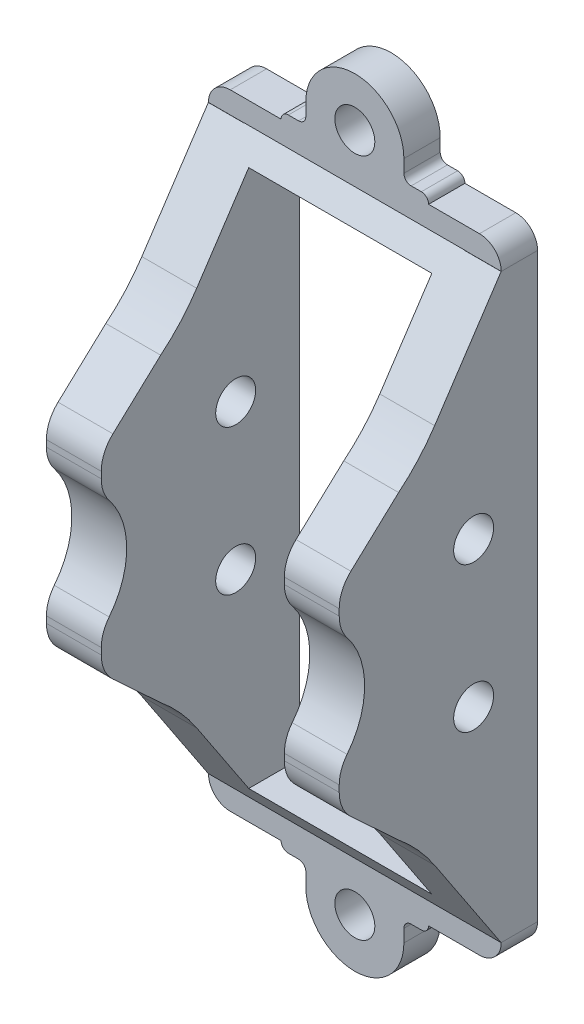
SolidWorks part; units mm, degrees
ref_plane "Front Plane" through (0, 0, 0) normal (0, 0, 1) x (1, 0, 0)
ref_plane "Top Plane" through (0, 0, 0) normal (0, 1, 0) x (1, 0, 0)
ref_plane "Right Plane" through (0, 0, 0) normal (1, 0, 0) x (0, 0, -1)
sketch "Sketch2" plane through (0, 0, 0) normal (0, 0, 1) x (1, 0, 0)
  line L0 (-58.75, 18.25) -> (-58.75, 111.75)
  line L1 (-45.25, 111.75) -> (-45.25, 18.25)
  line L3 (-56.225, 25) -> (-47.775, 25)
  line L4 (-56.225, 25) -> (-56.225, 105)
  line L5 (-56.225, 105) -> (-47.775, 105)
  line L6 (-47.775, 25) -> (-47.775, 105)
  circle A0 centre (-52, 18.25) radius 2.75
  circle A1 centre (-52, 111.75) radius 2.75
  arc A2 (-45.25, 111.75) -> (-58.75, 111.75) centre (-52, 111.75) ccw
  arc A3 (-58.75, 18.25) -> (-45.25, 18.25) centre (-52, 18.25) ccw
  circle A4 centre (-52, 18.25) radius 6.75 construction
  circle A5 centre (-52, 111.75) radius 6.75 construction
  dimension "D1" = 4
extrude "Boss-Extrude1" add sketch "Sketch2" along normal blind 5
sketch "Sketch4" plane through (0, 0, 0) normal (0, 0, 1) x (1, 0, 0)
  line L1 (-52, 21) -> (-62.15, 21)
  line L2 (-62.15, 118.5) -> (-62.15, 75) construction
  line L3 (-62.15, 21) -> (-41.85, 21)
  line L4 (-41.85, 118.5) -> (-41.85, 75) construction
  line L5 (-52, 109) -> (-62.15, 109)
  line L6 (-62.15, 109) -> (-41.85, 109)
  line L7 (-41.85, 109) -> (-41.85, 21)
  line L8 (-62.15, 21) -> (-62.15, 109)
  circle A0 centre (-52, 18.25) radius 2.75 construction
  circle A1 centre (-52, 111.75) radius 2.75 construction
extrude "Boss-Extrude2" add sketch "Sketch4" along normal up to surface (5 mm away) up to face at (-49.25, 18.25, 5)
sketch "Sketch5" plane through (-41.85, 0, 0) normal (1, 0, 0) x (0, 0, -1)
  line L1 (-5, 21) -> (-5, 109) construction
  line L2 (-5, 24.978) -> (-5, 105.022)
  line L5 (-30, 75.022) -> (-30, 80.5271)
  line L10 (-30, 54.978) -> (-30, 49.4729)
  line L11 (-30, 75.022) -> (-30, 80.5271)
  line L12 (-14.1667, 38.7973) -> (-5, 24.978)
  line L15 (-14.1667, 91.2027) -> (-5, 105.022)
  arc A0 (-30, 54.978) -> (-30, 75.022) centre (-35, 65) ccw
  arc A1 (-30, 80.5271) -> (-14.1667, 91.2027) centre (-35, 105.022) ccw
  arc A2 (-14.1667, 38.7973) -> (-30, 49.4729) centre (-35, 24.978) ccw
  line M14 (-5, 109) -> (-5, 21)
  dimension "D2" = 22.4
  dimension "D6" = 50
extrude "Boss-Extrude3" add sketch "Sketch5" against normal up to surface (20.3 mm away) contours A2 L12 L15 A1 L5 A0 L10 M14 up to face at (-62.15, 65, 2.5)
fillet "Fillet3" radius 4.2 4 edges at (-52, 80.5271, 30) (-52, 54.978, 30) (-52, 75.022, 30) (-52, 49.4729, 30)
sketch "Sketch7" plane through (0, 0, 5) normal (0, 0, -1) x (-1, 0, 0)
  line L1 (47.775, 25) -> (56.225, 25)
  line L2 (47.775, 25) -> (47.775, 105)
  line L3 (47.775, 105) -> (56.225, 105)
  line L4 (56.225, 25) -> (56.225, 105)
extrude "Cut-Extrude1" cut sketch "Sketch7" against normal blind 38
fillet "Fillet4" radius 3 4 edges at (-47.775, 105, 2.5073) (-56.225, 105, 2.5073) (-56.225, 25, 2.5073) (-47.775, 25, 2.5073)
fillet "Fillet5" radius 1 8 edges at (-62.15, 109, 2.5) (-58.75, 109, 2.5) (-45.25, 109, 2.5) (-41.85, 109, 2.5) (-62.15, 21, 2.5) (-58.75, 21, 2.5) (-41.85, 21, 2.5) (-45.25, 21, 2.5)
sketch "Sketch8" plane through (-41.85, 0, 0) normal (1, 0, 0) x (0, 0, -1)
  line L7 (0, 22) -> (0, 108)
  line L8 (0, 108) -> (-5, 108)
  line L9 (-5, 108) -> (-5, 105.022)
  line L10 (-5, 105.022) -> (-14.1667, 91.2027)
  line L11 (-14.1667, 38.7973) -> (-5, 24.978)
  line L12 (-5, 24.978) -> (-5, 22)
  line L13 (-5, 22) -> (0, 22)
  line L14 (0, 22) -> (0, 108)
  line L15 (0, 108) -> (-5, 108)
  line L16 (-5, 108) -> (-5, 105.022)
  line L17 (-5, 105.022) -> (-14.1667, 91.2027)
  line L18 (-14.1667, 38.7973) -> (-5, 24.978)
  line L19 (-5, 24.978) -> (-5, 22)
  line L20 (-5, 22) -> (0, 22)
  arc A7 (-27.1233, 81.2953) -> (-14.1667, 91.2027) centre (-35, 105.022) ccw
  arc A8 (-27.1233, 81.2953) -> (-30, 77.3295) centre (-25.8, 77.3092) ccw
  arc A9 (-30, 77.3295) -> (-28.3091, 73.9817) centre (-25.8, 77.3499) ccw
  arc A10 (-28.3091, 56.0183) -> (-28.3091, 73.9817) centre (-35, 65) ccw
  arc A11 (-28.3091, 56.0183) -> (-30, 52.6705) centre (-25.8, 52.6501) ccw
  arc A12 (-30, 52.6705) -> (-27.1233, 48.7047) centre (-25.8, 52.6908) ccw
  arc A13 (-14.1667, 38.7973) -> (-27.1233, 48.7047) centre (-35, 24.978) ccw
  arc A14 (-27.1233, 81.2953) -> (-14.1667, 91.2027) centre (-35, 105.022) ccw
  arc A15 (-27.1233, 81.2953) -> (-30, 77.3295) centre (-25.8, 77.3092) ccw
  arc A16 (-30, 77.3295) -> (-28.3091, 73.9817) centre (-25.8, 77.3499) ccw
  arc A17 (-28.3091, 56.0183) -> (-28.3091, 73.9817) centre (-35, 65) ccw
  arc A18 (-28.3091, 56.0183) -> (-30, 52.6705) centre (-25.8, 52.6501) ccw
  arc A19 (-30, 52.6705) -> (-27.1233, 48.7047) centre (-25.8, 52.6908) ccw
  arc A20 (-14.1667, 38.7973) -> (-27.1233, 48.7047) centre (-35, 24.978) ccw
  dimension "D1" = 0
extrude "Boss-Extrude4" add sketch "Sketch8" along normal blind 5
sketch "Sketch9" plane through (-62.15, 0, 0) normal (-1, 0, 0) x (0, 0, 1)
  line L7 (5, 105.022) -> (5, 108)
  line L8 (5, 108) -> (0, 108)
  line L9 (0, 108) -> (0, 22)
  line L10 (0, 22) -> (5, 22)
  line L11 (5, 22) -> (5, 24.978)
  line L12 (5, 24.978) -> (14.1667, 38.7973)
  line L13 (14.1667, 91.2027) -> (5, 105.022)
  line L14 (5, 105.022) -> (5, 108)
  line L15 (5, 108) -> (0, 108)
  line L16 (0, 108) -> (0, 22)
  line L17 (0, 22) -> (5, 22)
  line L18 (5, 22) -> (5, 24.978)
  line L19 (5, 24.978) -> (14.1667, 38.7973)
  line L20 (14.1667, 91.2027) -> (5, 105.022)
  arc A7 (27.1233, 48.7047) -> (14.1667, 38.7973) centre (35, 24.978) ccw
  arc A8 (27.1233, 48.7047) -> (30, 52.6705) centre (25.8, 52.6908) ccw
  arc A9 (30, 52.6705) -> (28.3091, 56.0183) centre (25.8, 52.6501) ccw
  arc A10 (28.3091, 73.9817) -> (28.3091, 56.0183) centre (35, 65) ccw
  arc A11 (28.3091, 73.9817) -> (30, 77.3295) centre (25.8, 77.3499) ccw
  arc A12 (30, 77.3295) -> (27.1233, 81.2953) centre (25.8, 77.3092) ccw
  arc A13 (14.1667, 91.2027) -> (27.1233, 81.2953) centre (35, 105.022) ccw
  arc A14 (27.1233, 48.7047) -> (14.1667, 38.7973) centre (35, 24.978) ccw
  arc A15 (27.1233, 48.7047) -> (30, 52.6705) centre (25.8, 52.6908) ccw
  arc A16 (30, 52.6705) -> (28.3091, 56.0183) centre (25.8, 52.6501) ccw
  arc A17 (28.3091, 73.9817) -> (28.3091, 56.0183) centre (35, 65) ccw
  arc A18 (28.3091, 73.9817) -> (30, 77.3295) centre (25.8, 77.3499) ccw
  arc A19 (30, 77.3295) -> (27.1233, 81.2953) centre (25.8, 77.3092) ccw
  arc A20 (14.1667, 91.2027) -> (27.1233, 81.2953) centre (35, 105.022) ccw
  dimension "D1" = 0
extrude "Boss-Extrude5" add sketch "Sketch9" along normal blind 5
sketch "Sketch10" plane through (-47.775, 0, 0) normal (-1, 0, 0) x (0, 0, 1)
  line L5 (14.1667, 91.2027) -> (7.0046, 102)
  line L6 (7.0046, 102) -> (0, 102)
  line L7 (0, 102) -> (0, 28)
  line L8 (0, 28) -> (7.0046, 28)
  line L9 (7.0046, 28) -> (14.1667, 38.7973)
  line L10 (14.1667, 91.2027) -> (7.0046, 102)
  line L11 (7.0046, 102) -> (0, 102)
  line L12 (0, 102) -> (0, 28)
  line L13 (0, 28) -> (7.0046, 28)
  line L14 (7.0046, 28) -> (14.1667, 38.7973)
  arc A7 (27.1233, 48.7047) -> (14.1667, 38.7973) centre (35, 24.978) ccw
  arc A8 (27.1233, 48.7047) -> (30, 52.6705) centre (25.8, 52.6908) ccw
  arc A9 (30, 52.6705) -> (28.3091, 56.0183) centre (25.8, 52.6501) ccw
  arc A10 (28.3091, 73.9817) -> (28.3091, 56.0183) centre (35, 65) ccw
  arc A11 (28.3091, 73.9817) -> (30, 77.3295) centre (25.8, 77.3499) ccw
  arc A12 (30, 77.3295) -> (27.1233, 81.2953) centre (25.8, 77.3092) ccw
  arc A13 (14.1667, 91.2027) -> (27.1233, 81.2953) centre (35, 105.022) ccw
  arc A14 (27.1233, 48.7047) -> (14.1667, 38.7973) centre (35, 24.978) ccw
  arc A15 (27.1233, 48.7047) -> (30, 52.6705) centre (25.8, 52.6908) ccw
  arc A16 (30, 52.6705) -> (28.3091, 56.0183) centre (25.8, 52.6501) ccw
  arc A17 (28.3091, 73.9817) -> (28.3091, 56.0183) centre (35, 65) ccw
  arc A18 (28.3091, 73.9817) -> (30, 77.3295) centre (25.8, 77.3499) ccw
  arc A19 (30, 77.3295) -> (27.1233, 81.2953) centre (25.8, 77.3092) ccw
  arc A20 (14.1667, 91.2027) -> (27.1233, 81.2953) centre (35, 105.022) ccw
  dimension "D1" = 0
extrude "Cut-Extrude2" cut sketch "Sketch10" against normal blind 5
sketch "Sketch11" plane through (-56.225, 0, 0) normal (1, 0, 0) x (0, 0, -1)
  line L5 (0, 28) -> (0, 102)
  line L6 (0, 102) -> (-7.0046, 102)
  line L7 (-7.0046, 102) -> (-14.1667, 91.2027)
  line L8 (-14.1667, 38.7973) -> (-7.0046, 28)
  line L9 (-7.0046, 28) -> (0, 28)
  line L10 (0, 28) -> (0, 102)
  line L11 (0, 102) -> (-7.0046, 102)
  line L12 (-7.0046, 102) -> (-14.1667, 91.2027)
  line L13 (-14.1667, 38.7973) -> (-7.0046, 28)
  line L14 (-7.0046, 28) -> (0, 28)
  arc A7 (-27.1233, 81.2953) -> (-14.1667, 91.2027) centre (-35, 105.022) ccw
  arc A8 (-27.1233, 81.2953) -> (-30, 77.3295) centre (-25.8, 77.3092) ccw
  arc A9 (-30, 77.3295) -> (-28.3091, 73.9817) centre (-25.8, 77.3499) ccw
  arc A10 (-28.3091, 56.0183) -> (-28.3091, 73.9817) centre (-35, 65) ccw
  arc A11 (-28.3091, 56.0183) -> (-30, 52.6705) centre (-25.8, 52.6501) ccw
  arc A12 (-30, 52.6705) -> (-27.1233, 48.7047) centre (-25.8, 52.6908) ccw
  arc A13 (-14.1667, 38.7973) -> (-27.1233, 48.7047) centre (-35, 24.978) ccw
  arc A14 (-27.1233, 81.2953) -> (-14.1667, 91.2027) centre (-35, 105.022) ccw
  arc A15 (-27.1233, 81.2953) -> (-30, 77.3295) centre (-25.8, 77.3092) ccw
  arc A16 (-30, 77.3295) -> (-28.3091, 73.9817) centre (-25.8, 77.3499) ccw
  arc A17 (-28.3091, 56.0183) -> (-28.3091, 73.9817) centre (-35, 65) ccw
  arc A18 (-28.3091, 56.0183) -> (-30, 52.6705) centre (-25.8, 52.6501) ccw
  arc A19 (-30, 52.6705) -> (-27.1233, 48.7047) centre (-25.8, 52.6908) ccw
  arc A20 (-14.1667, 38.7973) -> (-27.1233, 48.7047) centre (-35, 24.978) ccw
  dimension "D1" = 0
extrude "Cut-Extrude3" cut sketch "Sketch11" against normal blind 5
fillet "Fillet6" radius 3 4 edges at (-67.15, 22, 2.5) (-36.85, 22, 2.5) (-36.85, 108, 2.5) (-67.15, 108, 2.5)
sketch "Sketch12" plane through (0, 0, 0) normal (0, 0, -1) x (-1, 0, 0)
  line L0 (40, 55) -> (40, 100.8703)
  line L1 (42.775, 102) -> (40, 102)
  line L2 (40, 102) -> (64, 102)
  line L3 (40, 100.8703) -> (40, 102)
  line L4 (61.225, 28) -> (64, 28)
  line L5 (42.775, 28) -> (40, 28)
  line L6 (40, 55) -> (40, 28)
  line L7 (64, 75) -> (64, 102)
  line L8 (64, 102) -> (64, 28)
  line L9 (61.225, 28) -> (42.775, 28)
  line L10 (64.6, 102) -> (64.6, 27.4)
  line L11 (61.225, 27.4) -> (64.6, 27.4)
  line L12 (61.225, 27.4) -> (42.775, 27.4)
  line L13 (42.775, 27.4) -> (39.4, 27.4)
  line L14 (39.4, 55) -> (39.4, 27.4)
  line L15 (39.4, 55) -> (39.4, 100.8703)
  line L16 (39.4, 100.8703) -> (39.4, 102)
  line L17 (40, 102.6) -> (64, 102.6)
  line L18 (64.6, 102) -> (64.6, 102.6)
  line L19 (64, 102.6) -> (64.6, 102.6)
  line L20 (40, 102.6) -> (39.4, 102.6)
  line L21 (39.4, 102) -> (39.4, 102.6)
  line M4 (61.225, 102) -> (61.225, 28)
  line M5 (61.225, 28) -> (56.225, 28)
  arc M6 (56.225, 28) -> (53.225, 25) centre (53.225, 28) cw
  arc M8 (50.775, 25) -> (47.775, 28) centre (50.775, 28) cw
  line M9 (47.775, 28) -> (42.775, 28)
  line M10 (42.775, 28) -> (42.775, 102)
  line M11 (42.775, 102) -> (47.775, 102)
  arc M12 (47.775, 102) -> (50.775, 105) centre (50.775, 102) cw
  arc M14 (53.225, 105) -> (56.225, 102) centre (53.225, 102) cw
  line M15 (56.225, 102) -> (61.225, 102)
  dimension "D1" = 0.6
extrude "Cut-Extrude4" cut sketch "Sketch12" against normal through all both and the other way through all contours L9 L2 M5 M4 M15 M11 M10 M9 | L8 L7 L2 L4 M4 | L19 L17 L2 L7 L8 L4 L12 L11 L10 L18 M14 M15 M5 M6 | L12 L9 M6 M8 | L0 L6 L5 L1 L3 M10 | L21 L16 L15 L14 L13 L12 L5 L6 L0 L3 L1 L17 L20 M8 M9 M11 M12 | L17 L2 M12 M14
sketch "Sketch14" plane through (-36.85, 0, 0) normal (1, 0, 0) x (0, 0, -1)
  line L5 (-14.1667, 38.7973) -> (-5.0146, 25)
  line L6 (-5.0146, 25) -> (0, 25)
  line L7 (0, 25) -> (0, 105)
  line L8 (0, 105) -> (-5.0146, 105)
  line L9 (-5.0146, 105) -> (-14.1667, 91.2027)
  line L10 (-14.1667, 38.7973) -> (-5.0146, 25)
  line L11 (-5.0146, 25) -> (0, 25)
  line L12 (0, 25) -> (0, 105)
  line L13 (0, 105) -> (-5.0146, 105)
  line L14 (-5.0146, 105) -> (-14.1667, 91.2027)
  arc A7 (-27.1233, 81.2953) -> (-14.1667, 91.2027) centre (-35, 105.022) ccw
  arc A8 (-27.1233, 81.2953) -> (-30, 77.3295) centre (-25.8, 77.3092) ccw
  arc A9 (-30, 77.3295) -> (-28.3091, 73.9817) centre (-25.8, 77.3499) ccw
  arc A10 (-28.3091, 56.0183) -> (-28.3091, 73.9817) centre (-35, 65) ccw
  arc A11 (-28.3091, 56.0183) -> (-30, 52.6705) centre (-25.8, 52.6501) ccw
  arc A12 (-30, 52.6705) -> (-27.1233, 48.7047) centre (-25.8, 52.6908) ccw
  arc A13 (-14.1667, 38.7973) -> (-27.1233, 48.7047) centre (-35, 24.978) ccw
  arc A14 (-27.1233, 81.2953) -> (-14.1667, 91.2027) centre (-35, 105.022) ccw
  arc A15 (-27.1233, 81.2953) -> (-30, 77.3295) centre (-25.8, 77.3092) ccw
  arc A16 (-30, 77.3295) -> (-28.3091, 73.9817) centre (-25.8, 77.3499) ccw
  arc A17 (-28.3091, 56.0183) -> (-28.3091, 73.9817) centre (-35, 65) ccw
  arc A18 (-28.3091, 56.0183) -> (-30, 52.6705) centre (-25.8, 52.6501) ccw
  arc A19 (-30, 52.6705) -> (-27.1233, 48.7047) centre (-25.8, 52.6908) ccw
  arc A20 (-14.1667, 38.7973) -> (-27.1233, 48.7047) centre (-35, 24.978) ccw
  dimension "D1" = 0
extrude "Boss-Extrude6" add sketch "Sketch14" along normal blind 3
sketch "Sketch15" plane through (-67.15, 0, 0) normal (-1, 0, 0) x (0, 0, 1)
  line L5 (0, 105) -> (0, 25)
  line L6 (0, 25) -> (5.0146, 25)
  line L7 (5.0146, 25) -> (14.1667, 38.7973)
  line L8 (14.1667, 91.2027) -> (5.0146, 105)
  line L9 (5.0146, 105) -> (0, 105)
  line L10 (0, 105) -> (0, 25)
  line L11 (0, 25) -> (5.0146, 25)
  line L12 (5.0146, 25) -> (14.1667, 38.7973)
  line L13 (14.1667, 91.2027) -> (5.0146, 105)
  line L14 (5.0146, 105) -> (0, 105)
  arc A7 (27.1233, 48.7047) -> (14.1667, 38.7973) centre (35, 24.978) ccw
  arc A8 (27.1233, 48.7047) -> (30, 52.6705) centre (25.8, 52.6908) ccw
  arc A9 (30, 52.6705) -> (28.3091, 56.0183) centre (25.8, 52.6501) ccw
  arc A10 (28.3091, 73.9817) -> (28.3091, 56.0183) centre (35, 65) ccw
  arc A11 (28.3091, 73.9817) -> (30, 77.3295) centre (25.8, 77.3499) ccw
  arc A12 (30, 77.3295) -> (27.1233, 81.2953) centre (25.8, 77.3092) ccw
  arc A13 (14.1667, 91.2027) -> (27.1233, 81.2953) centre (35, 105.022) ccw
  arc A14 (27.1233, 48.7047) -> (14.1667, 38.7973) centre (35, 24.978) ccw
  arc A15 (27.1233, 48.7047) -> (30, 52.6705) centre (25.8, 52.6908) ccw
  arc A16 (30, 52.6705) -> (28.3091, 56.0183) centre (25.8, 52.6501) ccw
  arc A17 (28.3091, 73.9817) -> (28.3091, 56.0183) centre (35, 65) ccw
  arc A18 (28.3091, 73.9817) -> (30, 77.3295) centre (25.8, 77.3499) ccw
  arc A19 (30, 77.3295) -> (27.1233, 81.2953) centre (25.8, 77.3092) ccw
  arc A20 (14.1667, 91.2027) -> (27.1233, 81.2953) centre (35, 105.022) ccw
  dimension "D1" = 0
extrude "Boss-Extrude7" add sketch "Sketch15" along normal blind 3
sketch "Sketch17" plane through (-70.15, 0, 0) normal (-1, 0, 0) x (0, 0, 1)
  line L5 (5.0146, 105) -> (0, 105)
  line L6 (0, 105) -> (0, 25)
  line L7 (0, 25) -> (5.0146, 25)
  line L8 (5.0146, 25) -> (14.1667, 38.7973)
  line L9 (14.1667, 91.2027) -> (5.0146, 105)
  line L10 (5.0146, 105) -> (0, 105)
  line L11 (0, 105) -> (0, 25)
  line L12 (0, 25) -> (5.0146, 25)
  line L13 (5.0146, 25) -> (14.1667, 38.7973)
  line L14 (14.1667, 91.2027) -> (5.0146, 105)
  arc A7 (27.1233, 48.7047) -> (14.1667, 38.7973) centre (35, 24.978) ccw
  arc A8 (27.1233, 48.7047) -> (30, 52.6705) centre (25.8, 52.6908) ccw
  arc A9 (30, 52.6705) -> (28.3091, 56.0183) centre (25.8, 52.6501) ccw
  arc A10 (28.3091, 73.9817) -> (28.3091, 56.0183) centre (35, 65) ccw
  arc A11 (28.3091, 73.9817) -> (30, 77.3295) centre (25.8, 77.3499) ccw
  arc A12 (30, 77.3295) -> (27.1233, 81.2953) centre (25.8, 77.3092) ccw
  arc A13 (14.1667, 91.2027) -> (27.1233, 81.2953) centre (35, 105.022) ccw
  arc A14 (27.1233, 48.7047) -> (14.1667, 38.7973) centre (35, 24.978) ccw
  arc A15 (27.1233, 48.7047) -> (30, 52.6705) centre (25.8, 52.6908) ccw
  arc A16 (30, 52.6705) -> (28.3091, 56.0183) centre (25.8, 52.6501) ccw
  arc A17 (28.3091, 73.9817) -> (28.3091, 56.0183) centre (35, 65) ccw
  arc A18 (28.3091, 73.9817) -> (30, 77.3295) centre (25.8, 77.3499) ccw
  arc A19 (30, 77.3295) -> (27.1233, 81.2953) centre (25.8, 77.3092) ccw
  arc A20 (14.1667, 91.2027) -> (27.1233, 81.2953) centre (35, 105.022) ccw
  dimension "D1" = 0
extrude "Boss-Extrude8" add sketch "Sketch17" along normal blind 2
sketch "Sketch18" plane through (-33.85, 0, 0) normal (1, 0, 0) x (0, 0, -1)
  line L5 (-14.1667, 38.7973) -> (-5.0146, 25)
  line L6 (-5.0146, 25) -> (0, 25)
  line L7 (0, 25) -> (0, 105)
  line L8 (0, 105) -> (-5.0146, 105)
  line L9 (-5.0146, 105) -> (-14.1667, 91.2027)
  line L10 (-14.1667, 38.7973) -> (-5.0146, 25)
  line L11 (-5.0146, 25) -> (0, 25)
  line L12 (0, 25) -> (0, 105)
  line L13 (0, 105) -> (-5.0146, 105)
  line L14 (-5.0146, 105) -> (-14.1667, 91.2027)
  arc A7 (-14.1667, 38.7973) -> (-27.1233, 48.7047) centre (-35, 24.978) ccw
  arc A8 (-27.1233, 81.2953) -> (-14.1667, 91.2027) centre (-35, 105.022) ccw
  arc A9 (-27.1233, 81.2953) -> (-30, 77.3295) centre (-25.8, 77.3092) ccw
  arc A10 (-30, 77.3295) -> (-28.3091, 73.9817) centre (-25.8, 77.3499) ccw
  arc A11 (-28.3091, 56.0183) -> (-28.3091, 73.9817) centre (-35, 65) ccw
  arc A12 (-28.3091, 56.0183) -> (-30, 52.6705) centre (-25.8, 52.6501) ccw
  arc A13 (-30, 52.6705) -> (-27.1233, 48.7047) centre (-25.8, 52.6908) ccw
  arc A14 (-14.1667, 38.7973) -> (-27.1233, 48.7047) centre (-35, 24.978) ccw
  arc A15 (-27.1233, 81.2953) -> (-14.1667, 91.2027) centre (-35, 105.022) ccw
  arc A16 (-27.1233, 81.2953) -> (-30, 77.3295) centre (-25.8, 77.3092) ccw
  arc A17 (-30, 77.3295) -> (-28.3091, 73.9817) centre (-25.8, 77.3499) ccw
  arc A18 (-28.3091, 56.0183) -> (-28.3091, 73.9817) centre (-35, 65) ccw
  arc A19 (-28.3091, 56.0183) -> (-30, 52.6705) centre (-25.8, 52.6501) ccw
  arc A20 (-30, 52.6705) -> (-27.1233, 48.7047) centre (-25.8, 52.6908) ccw
  dimension "D1" = 0
extrude "Boss-Extrude9" add sketch "Sketch18" along normal blind 2
sketch "Sketch20" plane through (0, 0, 5) normal (0, 0, 1) x (1, 0, 0)
  line L0 (-64.15, 22) -> (-72.15, 22)
  line L1 (-72.15, 25) -> (-72.15, 22)
  line L2 (-39.85, 22) -> (-31.85, 22)
  line L3 (-31.85, 25) -> (-31.85, 22)
  line L4 (-31.85, 25) -> (-72.15, 25)
  line L5 (-64.15, 22) -> (-39.85, 22)
  line L6 (-72.15, 65) -> (-77.5172, 65)
  line L7 (-72.15, 73.9817) -> (-72.15, 56.0183) construction
  line L8 (-64.15, 108) -> (-39.85, 108)
  line L9 (-31.85, 105) -> (-72.15, 105)
  line L10 (-31.85, 105) -> (-31.85, 108)
  line L11 (-39.85, 108) -> (-31.85, 108)
  line L12 (-72.15, 105) -> (-72.15, 108)
  line L13 (-64.15, 108) -> (-72.15, 108)
  line M2 (-36.8501, 24.978) -> (-67.1499, 24.978)
  arc M3 (-67.1499, 24.978) -> (-64.15, 22) centre (-64.15, 25) ccw
  line M4 (-64.15, 22) -> (-62.15, 22)
  line M14 (-41.85, 22) -> (-39.85, 22)
  arc M15 (-39.85, 22) -> (-36.8501, 24.978) centre (-39.85, 25) ccw
extrude "Boss-Extrude10" add sketch "Sketch20" against normal up to surface (5 mm away) contours L8 L13 L12 L9 L10 L11 | L3 L4 L1 L0 L2 M3 M2 M15 | L5 M4 M14 M15 M2 M3 up to face at (-49.25, 18.25, 0)
fillet "Fillet8" radius 3 4 edges at (-31.85, 108, 2.5) (-72.15, 108, 2.5) (-31.85, 22, 2.5) (-72.15, 22, 2.5)
sketch "Sketch21" plane through (-31.85, 0, 0) normal (1, 0, 0) x (0, 0, -1)
  circle A0 centre (-8.8, 55) radius 2.75
  circle A1 centre (-8.8, 75) radius 2.75
extrude "Cut-Extrude5" cut sketch "Sketch21" against normal through all both and the other way through all
sketch "Sketch24" plane through (-31.85, 0, 0) normal (1, 0, 0) x (0, 0, -1)
  line L0 (0, 25) -> (0, 28)
  line L1 (0, 28) -> (-7.0046, 28)
  line L2 (-23.8, 65) -> (-32.5249, 65)
  line L3 (0, 102) -> (-7.0046, 102)
  line L7 (0, 25) -> (0, 105)
  line L8 (0, 105) -> (-5, 105)
  line L9 (-5, 105) -> (-5.0146, 105)
  line L10 (-5.0146, 105) -> (-14.1667, 91.2027)
  line L11 (-14.1667, 38.7973) -> (-5.0146, 25)
  line L12 (-5.0146, 25) -> (-5, 25)
  line L13 (-5, 25) -> (0, 25)
  line L14 (0, 25) -> (0, 105)
  line L15 (0, 105) -> (-5, 105)
  line L16 (-5, 105) -> (-5.0146, 105)
  line L17 (-5.0146, 105) -> (-14.1667, 91.2027)
  line L18 (-14.1667, 38.7973) -> (-5.0146, 25)
  line L19 (-5.0146, 25) -> (-5, 25)
  line L20 (-5, 25) -> (0, 25)
  arc A7 (-27.1233, 81.2953) -> (-14.1667, 91.2027) centre (-35, 105.022) ccw
  arc A8 (-27.1233, 81.2953) -> (-30, 77.3295) centre (-25.8, 77.3092) ccw
  arc A9 (-30, 77.3295) -> (-28.3091, 73.9817) centre (-25.8, 77.3499) ccw
  arc A10 (-28.3091, 56.0183) -> (-28.3091, 73.9817) centre (-35, 65) ccw
  arc A11 (-28.3091, 56.0183) -> (-30, 52.6705) centre (-25.8, 52.6501) ccw
  arc A12 (-30, 52.6705) -> (-27.1233, 48.7047) centre (-25.8, 52.6908) ccw
  arc A13 (-14.1667, 38.7973) -> (-27.1233, 48.7047) centre (-35, 24.978) ccw
  arc A14 (-27.1233, 81.2953) -> (-14.1667, 91.2027) centre (-35, 105.022) ccw
  arc A15 (-27.1233, 81.2953) -> (-30, 77.3295) centre (-25.8, 77.3092) ccw
  arc A16 (-30, 77.3295) -> (-28.3091, 73.9817) centre (-25.8, 77.3499) ccw
  arc A17 (-28.3091, 56.0183) -> (-28.3091, 73.9817) centre (-35, 65) ccw
  arc A18 (-28.3091, 56.0183) -> (-30, 52.6705) centre (-25.8, 52.6501) ccw
  arc A19 (-30, 52.6705) -> (-27.1233, 48.7047) centre (-25.8, 52.6908) ccw
  arc A20 (-14.1667, 38.7973) -> (-27.1233, 48.7047) centre (-35, 24.978) ccw
  line M20 (0, 25) -> (0, 105)
  line M21 (0, 105) -> (-5, 105)
  line M22 (-5, 105) -> (-5.0146, 105)
  line M23 (-5.0146, 105) -> (-14.1667, 91.2027)
  line M31 (-14.1667, 38.7973) -> (-5.0146, 25)
  line M32 (-5.0146, 25) -> (-5, 25)
  line M33 (-5, 25) -> (0, 25)
  dimension "D2" = 3
  dimension "D1" = 0
extrude "Boss-Extrude11" add sketch "Sketch24" against normal up to surface (40.3 mm away) contours L3 M20 M21 M22 M23 | L1 M20 M31 M32 M33 up to face at (-72.15, 55, 6.05)
sketch "Sketch28" plane through (-72.15, 0, 0) normal (-1, 0, 0) x (0, 0, 1)
  line L0 (23.8, 65) -> (27.3, 65)
  line L1 (27.3, 65) -> (27.3, 87.6424)
  line L2 (27.3, 87.6424) -> (27.3, 38.524)
  line L3 (30, 77.3295) -> (30, 52.6705)
  arc A0 (28.3091, 73.9817) -> (28.3091, 56.0183) centre (35, 65) ccw construction
  arc A1 (27.1233, 48.7047) -> (30, 52.6705) centre (25.8, 52.6908) ccw construction
  arc A2 (30, 52.6705) -> (28.3091, 56.0183) centre (25.8, 52.6501) ccw construction
  arc A3 (28.3091, 73.9817) -> (30, 77.3295) centre (25.8, 77.3499) ccw construction
  arc A4 (30, 77.3295) -> (27.1233, 81.2953) centre (25.8, 77.3092) ccw construction
  arc A5 (27.1233, 48.7047) -> (30, 52.6705) centre (25.8, 52.6908) ccw
  arc A6 (30, 52.6705) -> (28.3091, 56.0183) centre (25.8, 52.6501) ccw
  arc A7 (28.3091, 73.9817) -> (28.3091, 56.0183) centre (35, 65) ccw
  arc A8 (28.3091, 73.9817) -> (30, 77.3295) centre (25.8, 77.3499) ccw
  arc A9 (30, 77.3295) -> (27.1233, 81.2953) centre (25.8, 77.3092) ccw
  arc M7 (27.1233, 48.7047) -> (30, 52.6705) centre (25.8, 52.6908) ccw
  arc M8 (30, 52.6705) -> (28.3091, 56.0183) centre (25.8, 52.6501) ccw
  arc M9 (28.3091, 56.0183) -> (28.3091, 73.9817) centre (35, 65) cw
  arc M10 (28.3091, 73.9817) -> (30, 77.3295) centre (25.8, 77.3499) ccw
  arc M11 (30, 77.3295) -> (27.1233, 81.2953) centre (25.8, 77.3092) ccw
  dimension "D1" = 3.5
extrude "Cut-Extrude6" cut sketch "Sketch28" against normal through all both and the other way through all contours L1 M9 M10 M11 | L2 M9 M7 M8
sketch "Sketch30" plane through (-72.15, 0, 0) normal (-1, 0, 0) x (0, 0, 1)
  line L0 (27.3, 73.1333) -> (27.3, 78.1333)
  line L1 (27.3, 56.8667) -> (27.3, 51.8667)
  line L2 (19.1259, 85.7084) -> (27.3, 78.1333)
  line L3 (19.1259, 44.2916) -> (27.3, 51.8667)
  line L13 (27.3, 73.1333) -> (27.3, 81.2322)
  line L14 (14.1667, 91.2027) -> (5.0146, 105)
  line L15 (5.0146, 105) -> (5, 105)
  line L16 (5, 105) -> (0, 105)
  line L17 (0, 105) -> (0, 25)
  line L18 (0, 25) -> (5, 25)
  line L19 (5, 25) -> (5.0146, 25)
  line L20 (5.0146, 25) -> (14.1667, 38.7973)
  line L21 (27.3, 48.7678) -> (27.3, 56.8667)
  line L22 (27.3, 73.1333) -> (27.3, 81.2322)
  line L23 (14.1667, 91.2027) -> (5.0146, 105)
  line L24 (5.0146, 105) -> (5, 105)
  line L25 (5, 105) -> (0, 105)
  line L26 (0, 105) -> (0, 25)
  line L27 (0, 25) -> (5, 25)
  line L28 (5, 25) -> (5.0146, 25)
  line L29 (5.0146, 25) -> (14.1667, 38.7973)
  line L30 (27.3, 48.7678) -> (27.3, 56.8667)
  arc A1 (14.1667, 91.2027) -> (27.1233, 81.2953) centre (35, 105.022) ccw construction
  arc A2 (27.1233, 48.7047) -> (14.1667, 38.7973) centre (35, 24.978) ccw construction
  arc A8 (27.3, 73.1333) -> (27.3, 56.8667) centre (35, 65) ccw
  arc A9 (27.3, 81.2322) -> (27.1233, 81.2953) centre (25.8, 77.3092) ccw
  arc A10 (14.1667, 91.2027) -> (27.1233, 81.2953) centre (35, 105.022) ccw
  arc A11 (27.1233, 48.7047) -> (14.1667, 38.7973) centre (35, 24.978) ccw
  arc A12 (27.1233, 48.7047) -> (27.3, 48.7678) centre (25.8, 52.6908) ccw
  arc A13 (27.3, 73.1333) -> (27.3, 56.8667) centre (35, 65) ccw
  arc A14 (27.3, 81.2322) -> (27.1233, 81.2953) centre (25.8, 77.3092) ccw
  arc A15 (14.1667, 91.2027) -> (27.1233, 81.2953) centre (35, 105.022) ccw
  arc A16 (27.1233, 48.7047) -> (14.1667, 38.7973) centre (35, 24.978) ccw
  arc A17 (27.1233, 48.7047) -> (27.3, 48.7678) centre (25.8, 52.6908) ccw
  line M38 (27.3, 73.1333) -> (27.3, 81.2322)
  arc M39 (27.3, 81.2322) -> (27.1233, 81.2953) centre (25.8, 77.3092) ccw
  arc M40 (27.1233, 81.2953) -> (14.1667, 91.2027) centre (35, 105.022) cw
  arc M48 (14.1667, 38.7973) -> (27.1233, 48.7047) centre (35, 24.978) cw
  arc M49 (27.1233, 48.7047) -> (27.3, 48.7678) centre (25.8, 52.6908) ccw
  line M50 (27.3, 48.7678) -> (27.3, 56.8667)
  dimension "D1" = 5
  dimension "D2" = 5
  dimension "D3" = 0
extrude "Cut-Extrude7" cut sketch "Sketch30" against normal through all both and the other way through all contours L2 M40 M38 M39 | L3 M48 M49 M50
fillet "Fillet9" radius 5 8 edges at (-35.625, 78.1333, 27.3) (-68.375, 73.1333, 27.3) (-68.375, 56.8667, 27.3) (-68.375, 78.1333, 27.3) (-35.625, 51.8667, 27.3) (-68.375, 51.8667, 27.3)
